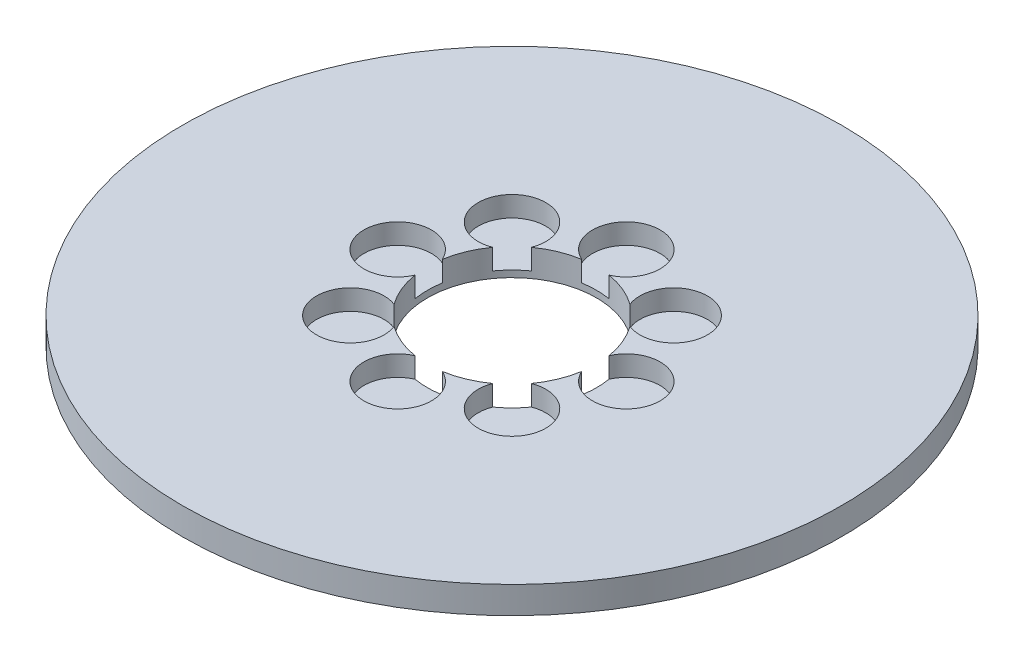
SolidWorks part; units mm, degrees
ref_plane "Front Plane" through (0, 0, 0) normal (0, 0, 1) x (1, 0, 0)
ref_plane "Top Plane" through (0, 0, 0) normal (0, 1, 0) x (1, 0, 0)
ref_plane "Right Plane" through (0, 0, 0) normal (1, 0, 0) x (0, 0, -1)
sketch "Sketch1" plane through (0, 0, 0) normal (0, 1, 0) x (1, 0, 0)
  circle A0 centre (0, 0) radius 97.5
  dimension "FLANGE_OD" = 195
extrude "Boss-Extrude1" add sketch "Sketch1" along normal blind 8
sketch "Sketch2" plane through (0, 0, 0) normal (0, 1, 0) x (1, 0, 0)
  circle A0 centre (0, 0) radius 25
  dimension "BORE_D" = 50
extrude "Cut-Extrude1" cut sketch "Sketch2" along normal through all
sketch "Sketch3" plane through (0, 8, 0) normal (0, 1, 0) x (1, 0, 0)
  circle A0 centre (0, 0) radius 33.8209 construction
  circle A1 centre (-33.8209, 0) radius 10
  dimension "BOLT_D" = 20
  dimension "BOLT_PCD" = 67.6417
extrude "Cut-Extrude2" cut sketch "Sketch3" against normal blind 6.0435
pattern_circular "CirPattern1" count 8 over 360 about axis through (0, 0, 0) along (0, 1, 0) of "Cut-Extrude2"
